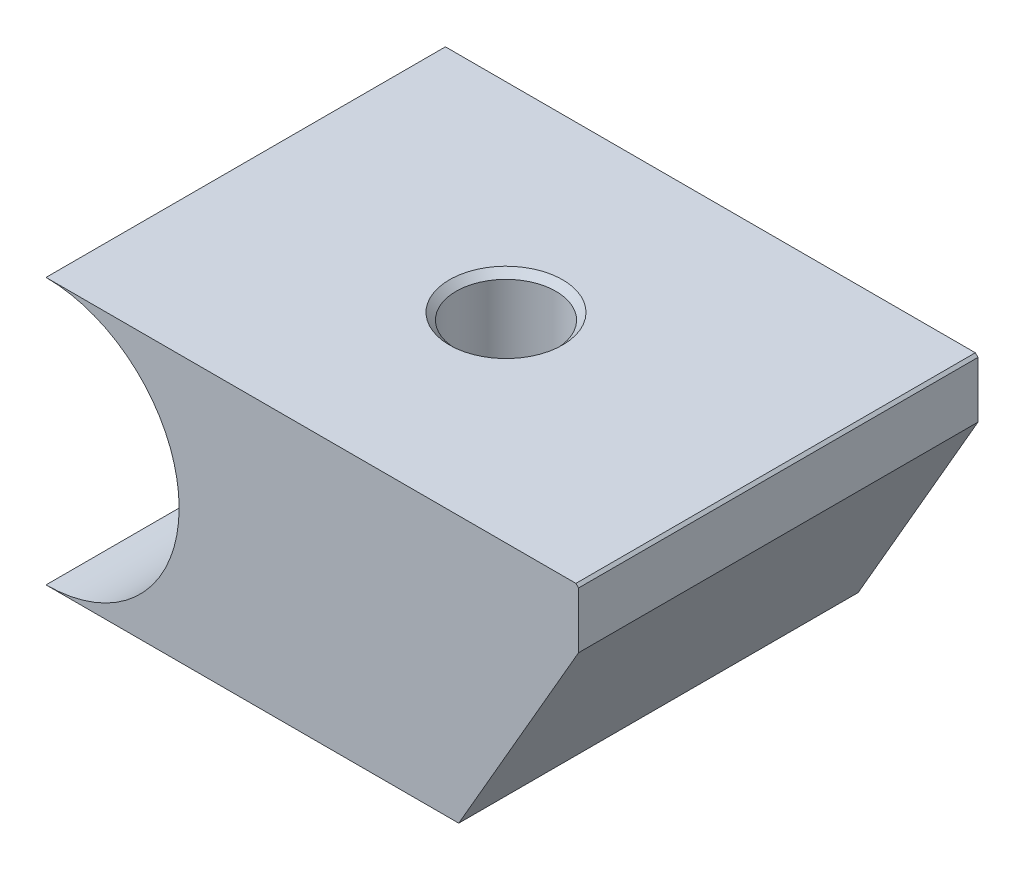
SolidWorks part; units mm, degrees
ref_plane "Front Plane" through (0, 0, 0) normal (0, 0, 1) x (1, 0, 0)
ref_plane "Top Plane" through (0, 0, 0) normal (0, 1, 0) x (1, 0, 0)
ref_plane "Right Plane" through (0, 0, 0) normal (1, 0, 0) x (0, 0, -1)
sketch "Sketch1" plane through (0, 0, 0) normal (0, 0, 1) x (1, 0, 0)
  line L1 (0, 0) -> (50.8, 0)
  line L3 (0, 25.4) -> (50.8, 25.4)
  line L4 (50.8, 0) -> (50.8, 25.4)
  arc A1 (0, 0) -> (0, 25.4) centre (0, 12.7) ccw
  dimension "D2" = 25.4
  dimension "D1" = 50.8
extrude "Boss-Extrude1" add sketch "Sketch1" along normal blind 38.1
chamfer "Chamfer1" distance 11.43 angle 60 1 edges at (50.8, 0, 19.05) first distance on face at (25.4, 0, 19.05)
hole_wizard "3/8 (0.375) Diameter Hole1" positions "Sketch4" profile "Sketch3" hole size "3/8" standard "ANSI Inch" end condition through all
sketch "Sketch4" plane through (0, 25.4, 0) normal (0, 1, 0) x (1, 0, 0)
  line L0 (50.8, -38.1) -> (50.8, 0) construction
  point P0 (24.8285, -19.05)
  point P5 (50.8, -19.05)
  dimension "D1" = 25.9715
sketch "Sketch3" plane through (24.8285, 25.4, 19.05) normal (1, 0, 0) x (0, 0, 1)
  line L0 (0, 0) -> (0, 25.4)
  line L1 (0, 25.4) -> (4.7625, 25.4)
  line L2 (4.7625, 25.4) -> (4.7625, 0.635)
  line L3 (4.7625, 0.635) -> (5.3975, 0)
  line L5 (5.3975, 0) -> (0, 0)
  line L6 (-4.7625, 0.635) -> (-5.3975, 0) construction
  line L11 (0, -6.35) -> (0, 107.95) construction
  dimension "Thru Hole Dia." = 9.525
  dimension "Thru Hole Depth" = 25.4
  dimension "Near C'Sink Dia." = 10.795
  dimension "Near C'Sink Angle" = 90
chamfer "Chamfer2" distance 0.254 angle 45 1 edges at (50.8, 25.4, 19.05)
